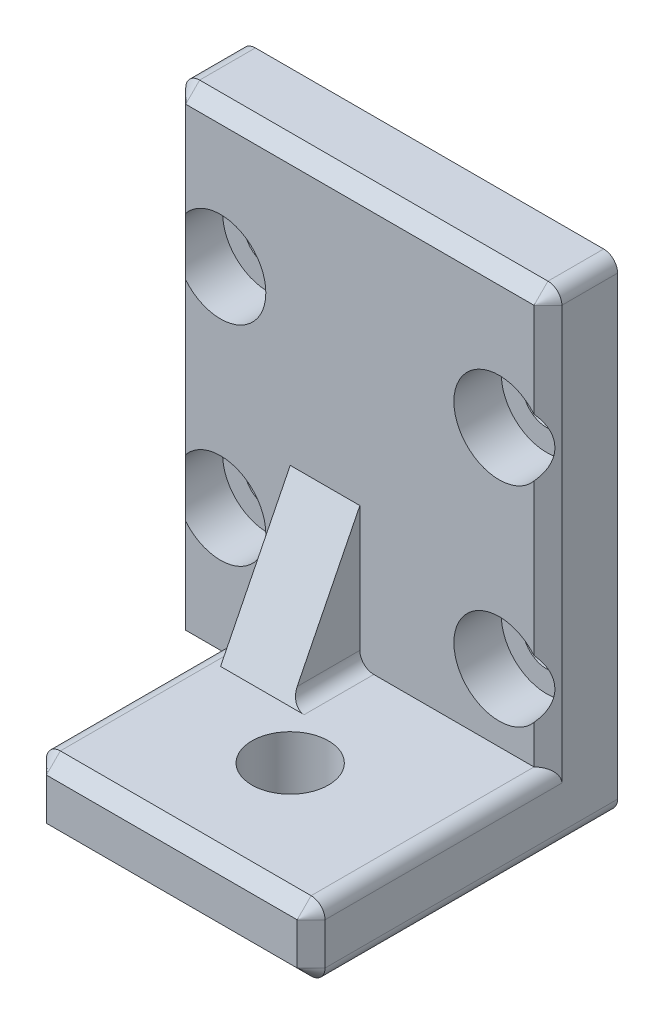
SolidWorks part; units mm, degrees
ref_plane "Front Plane" through (0, 0, 0) normal (0, 0, 1) x (1, 0, 0)
ref_plane "Top Plane" through (0, 0, 0) normal (0, 1, 0) x (1, 0, 0)
ref_plane "Right Plane" through (0, 0, 0) normal (1, 0, 0) x (0, 0, -1)
ref_plane "Rail Mount Front" through (0, 0, 5) normal (0, 0, 1) x (1, 0, 0)
ref_plane "ExtrusionMountFront" through (0, 0, 22) normal (0, 0, 1) x (1, 0, 0)
sketch "RailMountSketch" plane through (0, 0, 0) normal (0, 0, 1) x (1, 0, 0)
  line L1 (-13.5, 0) -> (13.5, 0)
  line L2 (-13.5, 0) -> (-13.5, 34.7)
  line L3 (-13.5, 34.7) -> (13.5, 34.7)
  line L4 (13.5, 0) -> (13.5, 34.7)
  line L5 (-10, 9.85) -> (10, 9.85) construction
  line L6 (-10, 9.85) -> (-10, 24.85) construction
  line L7 (-10, 24.85) -> (10, 24.85) construction
  line L8 (10, 9.85) -> (10, 24.85) construction
  line L9 (-10, 9.85) -> (10, 24.85) construction
  line L10 (-10, 24.85) -> (10, 9.85) construction
  line L11 (-6.5, 5) -> (13.5, 5) construction
  line L12 (-6.5, 5) -> (-6.5, 0) construction
  line L13 (-6.5, 0) -> (13.5, 0) construction
  line L14 (13.5, 5) -> (13.5, 0) construction
  line L15 (-6.5, 5) -> (13.5, 0) construction
  line L16 (-6.5, 0) -> (13.5, 5) construction
  point P4 (0, 17.35)
  point P12 (3.5, 2.5)
  dimension "D1" = 27
  dimension "D2" = 34.7
  dimension "D3" = 20
  dimension "D4" = 15
  dimension "D5" = 17.35
  dimension "D6" = 20
  dimension "D7" = 6.5
  dimension "D8" = 5
extrude "Rail Mount" add sketch "RailMountSketch" along normal up to surface (5 mm away) up to plane "Rail Mount Front"
ref_plane "ExtrusionMountingTopPlane" through (0, 5, 0) normal (0, 1, 0) x (1, 0, 0)
hole_wizard "Rail Mounting Holes" positions "Sketch2" profile "Sketch3" counterbore size "M3" standard "ISO" end condition through all
sketch "Sketch2" plane through (0, 0, 5) normal (0, 0, 1) x (1, 0, 0)
  point P0 (-10, 24.85)
  point P3 (10, 24.85)
  point P6 (10, 9.85)
  point P9 (-10, 9.85)
sketch "Sketch3" plane through (-10, 24.85, 5) normal (1, 0, 0) x (0, -1, 0)
  line L0 (0, 0) -> (0, 5)
  line L1 (0, 5) -> (1.7, 5)
  line L3 (1.7, 5) -> (1.7, 3.4)
  line L4 (1.7, 3.4) -> (3.25, 3.4)
  line L5 (3.25, 3.4) -> (3.25, 0)
  line L7 (3.25, 0) -> (0, 0)
  line L11 (0, -6.35) -> (0, 107.95) construction
  dimension "Thru Hole Dia." = 3.4
  dimension "Thru Hole Depth" = 5
  dimension "C'Bore Dia." = 6.5
  dimension "C'Bore Depth" = 3.4
sketch "ExtrusionMountSketch" plane through (0, 0, 5) normal (0, 0, 1) x (1, 0, 0)
  line L3 (-6.5, 5) -> (13.5, 5) construction
  line L4 (13.5, 5) -> (13.5, 0)
  line L7 (-6.5, 5) -> (13.5, 5)
  line L8 (-6.5, 5) -> (-6.5, 0)
  line L9 (-13.5, 0) -> (13.5, 0) construction
  line L10 (-6.5, 0) -> (13.5, 0)
extrude "ExtrusionMount" add sketch "ExtrusionMountSketch" along normal up to surface (17 mm away) up to plane "ExtrusionMountFront"
sketch "ExtrusionMountingHolePosition" plane through (0, 5, 0) normal (0, 1, 0) x (1, 0, 0)
  line L0 (3.5, -22) -> (3.5, -5)
  line L3 (-13.6459, -5) -> (13.6459, -5) construction
  line L4 (-13.6459, -22) -> (13.6459, -22) construction
  line L5 (-6.5, 0) -> (13.5, 0) construction
  line L6 (-6.5, 0) -> (13.5, 0) construction
  point P0 (3.5, -13.5)
  point P7 (3.5, -13.5)
  dimension "D1" = 10
hole_wizard "ExtrusionMountingHole" positions "Sketch8" profile "Sketch9" hole size "M5" standard "ISO" end condition through all
sketch "Sketch8" plane through (0, 5, 0) normal (0, 1, 0) x (1, 0, 0)
  point P0 (3.5, -13.5)
sketch "Sketch9" plane through (3.5, 5, 13.5) normal (1, 0, 0) x (0, 0, 1)
  line L0 (0, 0) -> (0, 5)
  line L1 (0, 5) -> (2.75, 5)
  line L2 (2.75, 5) -> (2.75, 0)
  line L5 (2.75, 0) -> (0, 0)
  line L11 (0, -6.35) -> (0, 107.95) construction
  dimension "Thru Hole Dia." = 5.5
  dimension "Thru Hole Depth" = 5
sketch "Webbing Sketch" plane through (0, 0, 0) normal (1, 0, 0) x (0, 0, -1)
  line L1 (-10, 5) -> (-5, 15)
  line L2 (-22, 5) -> (-5, 5) construction
  line L3 (-5, 13.6459) -> (-5, -13.6459) construction
  line L4 (-5, 15) -> (-5, 5)
  line L5 (-5, 5) -> (-10, 5)
  dimension "D1" = 5
  dimension "D2" = 10
extrude "Webbing" add sketch "Webbing Sketch" against normal blind 5
fillet "Print Helper Fillets" radius 1 8 edges at (0, 5, 7.5) (13.5, 5, 13.5) (-13.5, 34.7, 2.5) (13.5, 34.7, 2.5) (13.5, 0, 11) (-13.5, 0, 2.5) (-6.5, 5, 13.5) (-6.5, 0, 13.5)
chamfer "Cosmetic Chamfers" distance 1 angle 45 15 edges at (-13.5, 17.35, 5) (-13.2071, 34.4071, 5) (-9, 0, 5) (0, 34.7, 5) (13.2071, 34.4071, 5) (13.5, 18.85, 5) (13.5, 2.5, 22) (13.2071, 4.7071, 22) (3.5, 5, 22) (3.5, 0, 22) (13.2071, 0.2929, 22) (-6.2071, 0.2929, 22) (-6.5, 2.5, 22) (-6.2071, 4.7071, 22) (-13.2071, 0.2929, 5)
sketch "Rail Mounting Holes Positions" plane through (0, 0, 0) normal (0, 0, 1) x (1, 0, 0)
  point P0 (-10, 9.85)
  point P2 (10, 9.85)
  point P4 (10, 24.85)
  point P6 (-10, 24.85)
